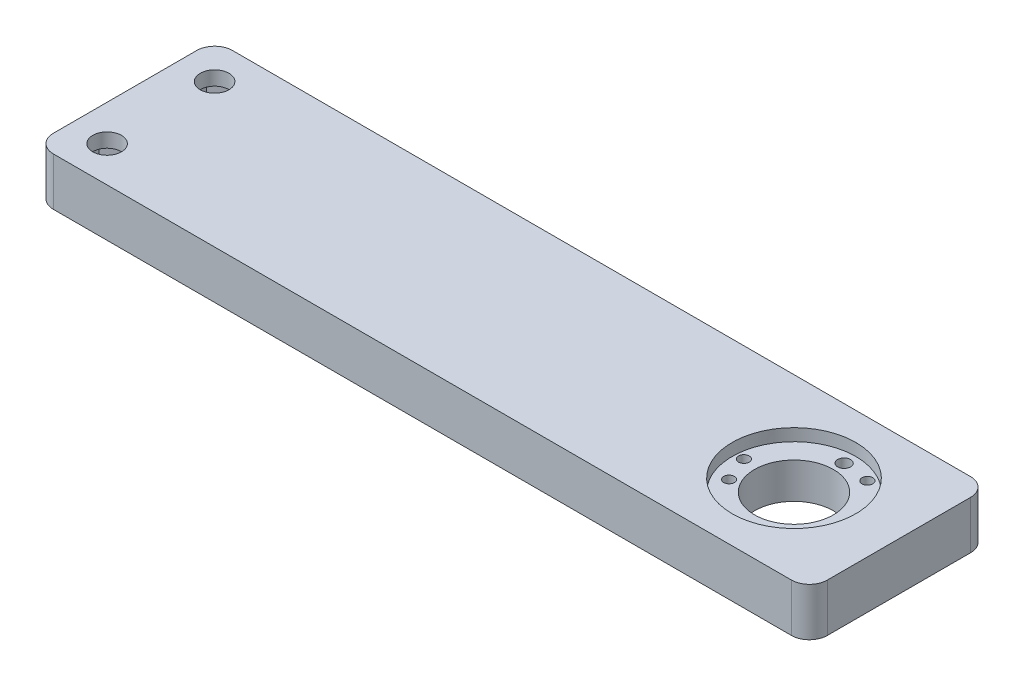
SolidWorks part; units mm, degrees
ref_plane "Front Plane" through (0, 0, 0) normal (0, 0, 1) x (1, 0, 0)
ref_plane "Top Plane" through (0, 0, 0) normal (0, 1, 0) x (1, 0, 0)
ref_plane "Right Plane" through (0, 0, 0) normal (1, 0, 0) x (0, 0, -1)
sketch "Sketch1" plane through (0, 0, 0) normal (0, 1, 0) x (1, 0, 0)
  line L1 (-103, -25) -> (103, -25)
  line L2 (-108, -20) -> (-108, 20)
  line L3 (-103, 25) -> (103, 25)
  line L4 (108, -20) -> (108, 20)
  line L5 (-108, -25) -> (108, 25) construction
  line L6 (-108, 25) -> (108, -25) construction
  arc A0 (103, 25) -> (108, 20) centre (103, 20) cw
  arc A1 (103, -25) -> (108, -20) centre (103, -20) ccw
  arc A2 (-103, -25) -> (-108, -20) centre (-103, -20) cw
  arc A3 (-108, 20) -> (-103, 25) centre (-103, 20) cw
  circle A4 centre (-98, 15) radius 4
  circle A5 centre (-98, -15) radius 4
  circle A6 centre (78.7, 0) radius 11
  circle A7 centre (78.7, 0) radius 19.3
  circle A8 centre (78.7, 14) radius 1.5
  circle A9 centre (86.2, 12.9904) radius 1.5
  circle A10 centre (90.8244, -7) radius 1.5
  circle A11 centre (86.2, -12.9904) radius 1.5
  circle A12 centre (63.7, 1.0089) radius 1.5
  circle A13 centre (66.5756, -5.9911) radius 1.5
  point P0 (0, 0)
  point P28 (78.7, 14)
  point P29 (86.2, 12.9904)
  point P30 (90.8244, -7)
  point P31 (86.2, -12.9904)
  point P32 (66.5756, -5.9911)
  point P33 (63.7, 1.0089)
  dimension "D3" = 5
  dimension "D4" = 8
  dimension "D5" = 8
  dimension "D10" = 22
  dimension "D11" = 38.6
  dimension "D13" = 14
  dimension "D24" = 3
  dimension "D25" = 3
  dimension "D26" = 3
  dimension "D27" = 3
  dimension "D28" = 3
  dimension "D29" = 3
  dimension "D1" = 216
  dimension "D2" = 50
  dimension "D6" = 10
  dimension "D7" = 10
  dimension "D8" = 10
  dimension "D9" = 10
  dimension "D12" = 176.7
  dimension "D14" = 7.5
  dimension "D15" = 12.9904
  dimension "D16" = 7.5677
  dimension "D17" = 12.1244
  dimension "D18" = 7.5
  dimension "D19" = 7.5
  dimension "D20" = 15
  dimension "D21" = 15
  dimension "D22" = 7
  dimension "D23" = 12.1244
extrude "Boss-Extrude1" add sketch "Sketch1" along normal blind 10 contours L3 A0 L4 A1 L1 A2 L2 A3 | A4 | A5 | A6 | A13 | A12 | A8 | A9 | A10 | A11
hole_wizard "CBORE for M3 Hex Socket Head Cap Screw1" positions "Sketch3" profile "Sketch4" counterbore size "M3" standard "ISO" end condition through all
sketch "Sketch3" plane through (0, 10, 0) normal (0, 1, 0) x (1, 0, 0)
  point P0 (78.7, 14)
sketch "Sketch4" plane through (78.7, 10, -14) normal (1, 0, 0) x (0, 0, 1)
  line L0 (0, 0) -> (0, 10)
  line L1 (0, 10) -> (1.8, 10)
  line L3 (1.8, 10) -> (1.8, 3.4)
  line L4 (3.25, 3.4) -> (1.8, 3.4)
  line L5 (3.25, 3.4) -> (3.25, 0.025)
  line L6 (3.25, 0.025) -> (3.275, 0)
  line L7 (3.275, 0) -> (0, 0)
  line L8 (-3.25, 0.025) -> (-3.275, 0) construction
  line L11 (0, -6.35) -> (0, 107.95) construction
  dimension "Thru Hole Dia." = 3.6
  dimension "Thru Hole Depth" = 10
  dimension "C'Bore Dia." = 6.5
  dimension "C'Bore Depth" = 3.4
  dimension "Near C'Sink Dia." = 6.55
  dimension "Near C'Sink Angle" = 90
sketch "Sketch5" plane through (0, 10, 0) normal (0, 1, 0) x (1, 0, 0)
  circle A0 centre (78.7, 0) radius 17.25
  dimension "D1" = 34.5
extrude "Cut-Extrude1" cut sketch "Sketch5" against normal up to surface (3.4 mm away) up to face at (78.7, 6.6, -14.125)
sketch "Sketch6" plane through (0, 0, 0) normal (0, -1, 0) x (1, 0, 0)
  line L0 (-78, 25) -> (-78, -25)
  line L4 (-103, -25) -> (103, -25)
  line L5 (108, -20) -> (108, 20)
  line L6 (103, 25) -> (-103, 25)
  line L7 (-108, 20) -> (-108, -20)
  line L8 (-103, -25) -> (103, -25)
  line L9 (108, -20) -> (108, 20)
  line L10 (103, 25) -> (-103, 25)
  line L11 (-108, 20) -> (-108, -20)
  circle A0 centre (-98, 15) radius 4 construction
  circle A1 centre (-98, -15) radius 4 construction
  circle A2 centre (63.7, -1.0089) radius 1.5 construction
  circle A3 centre (66.5756, 5.9911) radius 1.5 construction
  arc A4 (-108, -20) -> (-103, -25) centre (-103, -20) ccw
  arc A5 (103, -25) -> (108, -20) centre (103, -20) ccw
  arc A6 (108, 20) -> (103, 25) centre (103, 20) ccw
  arc A7 (-103, 25) -> (-108, 20) centre (-103, 20) ccw
  arc A8 (-108, -20) -> (-103, -25) centre (-103, -20) ccw
  arc A9 (103, -25) -> (108, -20) centre (103, -20) ccw
  arc A10 (108, 20) -> (103, 25) centre (103, 20) ccw
  arc A11 (-103, 25) -> (-108, 20) centre (-103, 20) ccw
  circle A12 centre (78.7, 0) radius 11 construction
  circle A13 centre (86.2, 12.9904) radius 1.5 construction
  circle A14 centre (90.8244, 7) radius 1.5 construction
  circle A15 centre (86.2, -12.9904) radius 1.5 construction
  circle A16 centre (78.7, -14) radius 1.8 construction
  circle A17 centre (78.7, -14) radius 1.8
  circle A18 centre (86.2, -12.9904) radius 1.5
  circle A19 centre (90.8244, 7) radius 1.5
  circle A20 centre (86.2, 12.9904) radius 1.5
  circle A21 centre (78.7, 0) radius 11
  circle A22 centre (66.5756, 5.9911) radius 1.5
  circle A23 centre (63.7, -1.0089) radius 1.5
  circle A24 centre (-98, -15) radius 4
  circle A25 centre (-98, 15) radius 4
  circle M10 centre (78.7, -14) radius 1.8
  circle M11 centre (90.8244, 7) radius 1.5
  circle M12 centre (66.5756, 5.9911) radius 1.5
  circle M13 centre (-98, 15) radius 4
  arc M14 (-108, -20) -> (-103, -25) centre (-103, -20) ccw
  line M15 (-103, -25) -> (103, -25)
  arc M16 (103, -25) -> (108, -20) centre (103, -20) ccw
  line M17 (108, -20) -> (108, 20)
  arc M18 (108, 20) -> (103, 25) centre (103, 20) ccw
  line M19 (103, 25) -> (-103, 25)
  arc M20 (-103, 25) -> (-108, 20) centre (-103, 20) ccw
  line M21 (-108, 20) -> (-108, -20)
  circle M22 centre (-98, -15) radius 4
  circle M23 centre (78.7, 0) radius 11
  circle M24 centre (63.7, -1.0089) radius 1.5
  circle M25 centre (86.2, -12.9904) radius 1.5
  circle M26 centre (86.2, 12.9904) radius 1.5
  dimension "D2" = 30
  dimension "D1" = 0
extrude "Boss-Extrude2" add sketch "Sketch6" along normal blind 3.4 contours L0 M19 M15 M16 M17 M18 M10 M12 M23 M25 M26 M24 M11 | L0 M19 M20 M21 M14 M15 M13 M22 region at (11.8297, 0, 0.0065) region at (-92.5308, 0, 0)
ref_plane "Plane1" through (0, 3.3, 0) normal (0, 1, 0) x (1, 0, 0)
sketch "Sketch7" plane through (0, 3.3, 0) normal (0, 1, 0) x (1, 0, 0)
  line L0 (-108, -20) -> (-108, 20) construction
  line L1 (-92.5, 11.8246) -> (-92.5, 18.1754)
  line L2 (-92.5, 18.1754) -> (-98, 21.3509)
  line L3 (-98, 21.3509) -> (-103.5, 18.1754)
  line L4 (-103.5, 18.1754) -> (-103.5, 11.8246)
  line L5 (-103.5, 11.8246) -> (-98, 8.6491)
  line L6 (-98, 8.6491) -> (-92.5, 11.8246)
  line L7 (-92.5, -18.1754) -> (-92.5, -11.8246)
  line L8 (-92.5, -11.8246) -> (-98, -8.6491)
  line L9 (-98, -8.6491) -> (-103.5, -11.8246)
  line L10 (-103.5, -11.8246) -> (-103.5, -18.1754)
  line L11 (-103.5, -18.1754) -> (-98, -21.3509)
  line L12 (-98, -21.3509) -> (-92.5, -18.1754)
  circle A0 centre (-98, 15) radius 5.5 construction
  circle A1 centre (-98, -15) radius 5.5 construction
  point P20 (-92.5, 15)
  dimension "D1" = 11
extrude "Cut-Extrude2" cut sketch "Sketch7" against normal blind 2.75 and the other way blind 2.75
